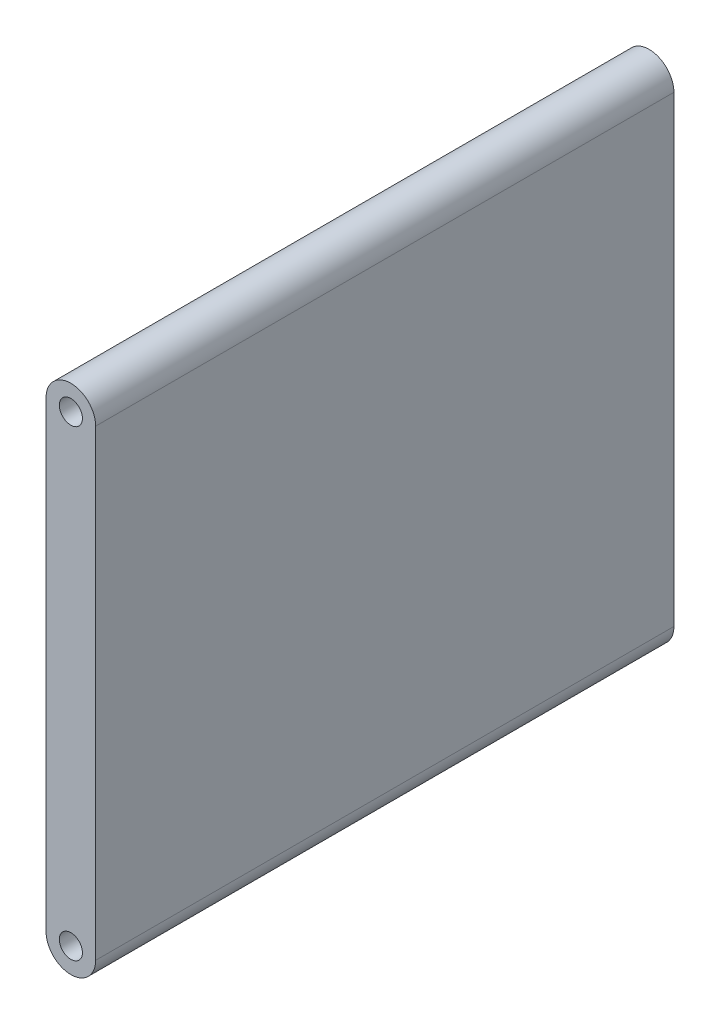
SolidWorks part; units mm, degrees
ref_plane "Alzado" through (0, 0, 0) normal (0, 0, 1) x (1, 0, 0)
ref_plane "Planta" through (0, 0, 0) normal (0, 1, 0) x (1, 0, 0)
ref_plane "Vista lateral" through (0, 0, 0) normal (1, 0, 0) x (0, 0, -1)
sketch "Croquis1" plane through (0, 0, 0) normal (0, 0, 1) x (1, 0, 0)
  line L0 (0, -28) -> (0, 28) construction
  line L1 (3, -28) -> (3, 28)
  line L2 (-3, -28) -> (-3, 28)
  circle A0 centre (0, 0) radius 32 construction
  arc A2 (3, -28) -> (-3, -28) centre (0, -28) cw
  arc A3 (3, 28) -> (-3, 28) centre (0, 28) ccw
  circle A4 centre (0, 28) radius 1.4
  circle A5 centre (0, -28) radius 1.4
  point P6 (0, 0)
  dimension "D1" = 64
  dimension "D5" = 2.8
  dimension "D2" = 56
  dimension "D3" = 3
  dimension "D4" = 3
extrude "Saliente-Extruir1" add sketch "Croquis1" along normal blind 70
